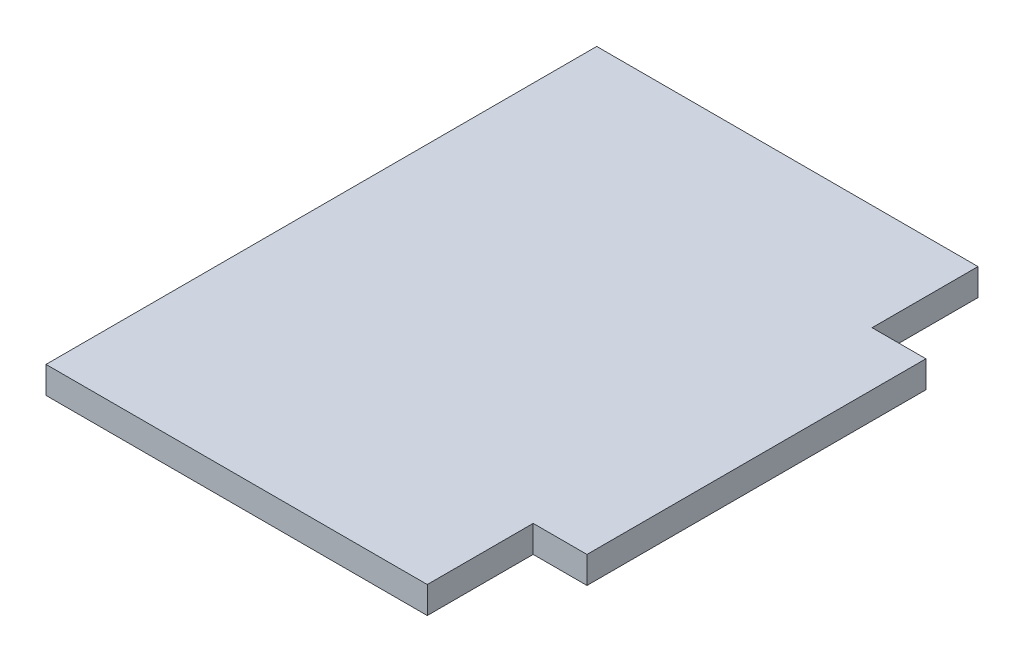
SolidWorks part; units mm, degrees
material "Cedar"
ref_plane "Front Plane" through (0, 0, 0) normal (0, 0, 1) x (1, 0, 0)
ref_plane "Top Plane" through (0, 0, 0) normal (0, 1, 0) x (1, 0, 0)
ref_plane "Right Plane" through (0, 0, 0) normal (1, 0, 0) x (0, 0, -1)
sketch "Sketch1" plane through (0, 0, 0) normal (0, 1, 0) x (1, 0, 0)
  line L0 (-22.5, 12.5) -> (22.5, 12.5)
  line L1 (22.5, 12.5) -> (22.5, 0)
  line L2 (22.5, 0) -> (28.85, 0)
  line L3 (28.85, 0) -> (28.85, -40)
  line L4 (28.85, -40) -> (22.5, -40)
  line L5 (22.5, -40) -> (22.5, -52.5)
  line L6 (22.5, -52.5) -> (-22.5, -52.5)
  line L7 (-22.5, -52.5) -> (-22.5, -40)
  line L8 (-22.5, -40) -> (-28.85, -40)
  line L9 (-28.85, -40) -> (-28.85, 0)
  line L10 (-28.85, 0) -> (-22.5, 0)
  line L11 (-22.5, 0) -> (-22.5, 12.5)
  line L12 (-22.5, 0) -> (-22.5, -40) construction
  point P11 (0, 12.5)
  point P14 (-28.85, -20)
  dimension "D1" = 6.35
  dimension "D2" = 40
  dimension "D3" = 45
  dimension "D4" = 65
extrude "Boss-Extrude1" add sketch "Sketch1" along normal blind 3.175 contours L11 L12 L7 L6 L5 L4 L3 L2 L1 L0 region at (2.0514, 0, 20)
equation "\"length\"= 65mm"
equation "\"w_mach\"= 45mm"
equation "\"w_tab\"= 40mm"
equation "\"t_wood\"= 0.125in"
equation "\"t_side\"= 0.25in"
equation "\"D1@Sketch1\"=\"t_side\""
equation "\"D2@Sketch1\"=\"w_tab\""
equation "\"D3@Sketch1\"=\"w_mach\""
equation "\"D4@Sketch1\"=\"length\""
equation "\"D1@Boss-Extrude1\"=\"t_wood\""
